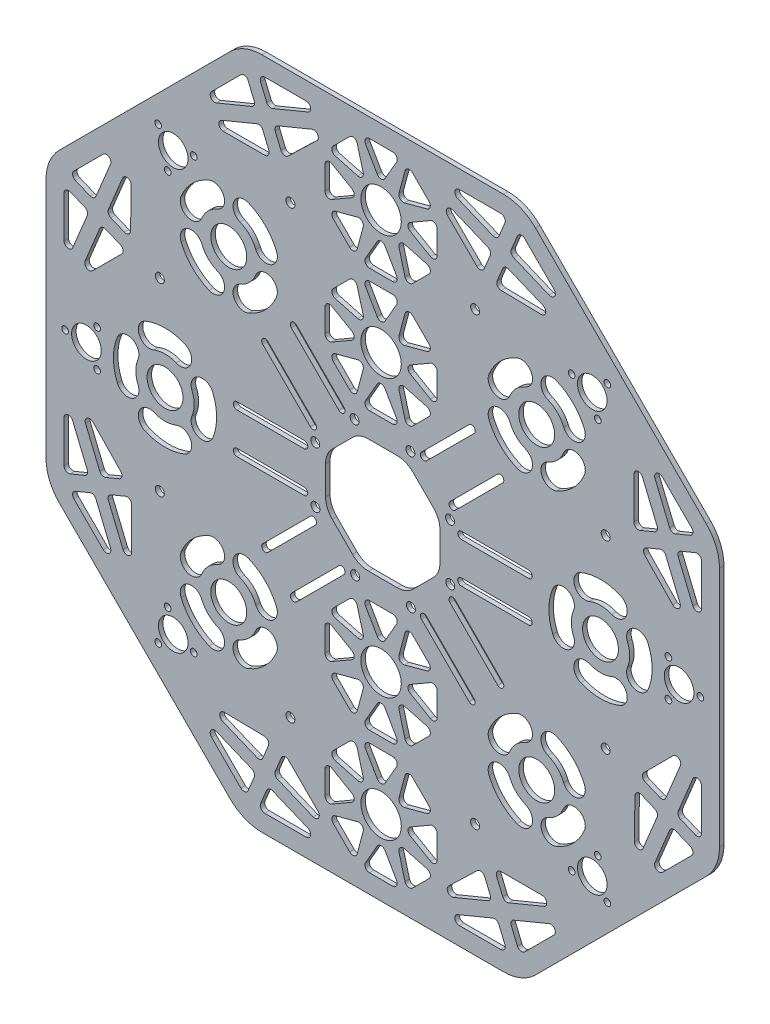
SolidWorks part; units mm, degrees
material "Thornel Mat VMA"
ref_plane "前视基准面" through (0, 0, 0) normal (0, 0, 1) x (1, 0, 0)
ref_plane "上视基准面" through (0, 0, 0) normal (0, 1, 0) x (1, 0, 0)
ref_plane "右视基准面" through (0, 0, 0) normal (1, 0, 0) x (0, 0, -1)
sketch "草图1" plane through (0, 0, 0) normal (0, 0, 1) x (1, 0, 0)
  line L1 (150, 62.132) -> (62.132, 150)
  line L2 (62.132, 150) -> (-62.132, 150)
  line L3 (-62.132, 150) -> (-150, 62.132)
  line L4 (-150, 62.132) -> (-150, -62.132)
  line L5 (-150, -62.132) -> (-62.132, -150)
  line L6 (-62.132, -150) -> (62.132, -150)
  line L7 (62.132, -150) -> (150, -62.132)
  line L8 (150, -62.132) -> (150, 62.132)
  circle A0 centre (0, 0) radius 150 construction
  dimension "D1" = 300
extrude "凸台-拉伸1" add sketch "草图1" along normal blind 2
sketch "草图2" plane through (0, 0, 0) normal (0, 0, -1) x (-1, 0, 0)
  line L0 (-150, -62.132) -> (-150, 62.132) construction
  circle A0 centre (-132, 0) radius 9.5 construction
  circle A1 centre (-132, 0) radius 6.6
  circle A2 centre (-141.5, 0) radius 1.5
  circle A3 centre (-127.25, 8.2272) radius 1.5
  circle A4 centre (-127.25, -8.2272) radius 1.5
  circle A5 centre (-93.3381, 93.3381) radius 6.6
  circle A6 centre (-100.0556, 100.0556) radius 1.5
  circle A7 centre (-84.1618, 95.7969) radius 1.5
  circle A8 centre (-95.7969, 84.1618) radius 1.5
  circle A9 centre (-93.3381, 93.3381) radius 9.5 construction
  circle A15 centre (93.3381, 93.3381) radius 6.6
  circle A16 centre (100.0556, 100.0556) radius 1.5
  circle A17 centre (95.7969, 84.1618) radius 1.5
  circle A18 centre (84.1618, 95.7969) radius 1.5
  circle A19 centre (93.3381, 93.3381) radius 9.5 construction
  circle A20 centre (132, 0) radius 6.6
  circle A21 centre (141.5, 0) radius 1.5
  circle A22 centre (127.25, -8.2272) radius 1.5
  circle A23 centre (127.25, 8.2272) radius 1.5
  circle A24 centre (132, 0) radius 9.5 construction
  circle A25 centre (93.3381, -93.3381) radius 6.6
  circle A26 centre (100.0556, -100.0556) radius 1.5
  circle A27 centre (84.1618, -95.7969) radius 1.5
  circle A28 centre (95.7969, -84.1618) radius 1.5
  circle A29 centre (93.3381, -93.3381) radius 9.5 construction
  circle A35 centre (-93.3381, -93.3381) radius 6.6
  circle A36 centre (-100.0556, -100.0556) radius 1.5
  circle A37 centre (-95.7969, -84.1618) radius 1.5
  circle A38 centre (-84.1618, -95.7969) radius 1.5
  circle A39 centre (-93.3381, -93.3381) radius 9.5 construction
  circle A128 centre (0, 132) radius 6.6
  circle A129 centre (0, 141.5) radius 1.5
  circle A130 centre (8.2272, 127.25) radius 1.5
  circle A131 centre (-8.2272, 127.25) radius 1.5
  circle A132 centre (0, -132) radius 6.6
  circle A133 centre (0, -141.5) radius 1.5
  circle A134 centre (-8.2272, -127.25) radius 1.5
  circle A135 centre (8.2272, -127.25) radius 1.5
  circle A136 centre (0, 132) radius 9.5 construction
  circle A137 centre (0, -132) radius 9.5 construction
  point P6 (0, -132)
  point P7 (-2.8868, -137)
  point P13 (-132, 0)
  point P14 (-137, 2.8868)
  point P19 (-93.3381, 93.3381)
  point P20 (-94.8324, 98.9149)
  point P23 (-93.3381, 93.3381)
  point P24 (0, -132)
  point P25 (0, 132)
  point P26 (2.8868, 137)
  point P31 (-132, 0)
  point P32 (0, 132)
  point P48 (93.3381, 93.3381)
  point P49 (98.9149, 94.8324)
  point P52 (93.3381, 93.3381)
  point P60 (132, 0)
  point P61 (137, -2.8868)
  point P64 (132, 0)
  point P72 (93.3381, -93.3381)
  point P73 (94.8324, -98.9149)
  point P76 (93.3381, -93.3381)
  point P96 (-93.3381, -93.3381)
  point P97 (-98.9149, -94.8324)
  point P100 (-93.3381, -93.3381)
  dimension "D1" = 19
  dimension "D2" = 13.2
  dimension "D3" = 3
  dimension "D5" = 18
  dimension "D4" = 3
  dimension "D6" = 8
extrude "切除-拉伸1" cut sketch "草图2" against normal blind 10
sketch "草图3" plane through (0, 0, 0) normal (0, 0, -1) x (-1, 0, 0)
  line L0 (0, 0) -> (-108.5837, 0) construction
  line L1 (-65, -7.4) -> (-65, -10.6) construction
  line L2 (-65, -7.4) -> (-35, -7.4)
  line L3 (-35, 7.4) -> (-35, 10.6) construction
  line L4 (-65, -10.6) -> (-35, -10.6)
  line L5 (-35, -7.4) -> (-35, -10.6) construction
  line L6 (-65, 7.4) -> (-65, 10.6) construction
  line L7 (-65, 10.6) -> (-35, 10.6)
  line L8 (-65, 7.4) -> (-35, 7.4)
  arc A0 (-65, -7.4) -> (-65, -10.6) centre (-65, -9) ccw
  arc A1 (-35, 10.6) -> (-35, 7.4) centre (-35, 9) cw
  arc A3 (-35, -10.6) -> (-35, -7.4) centre (-35, -9) ccw
  arc A4 (-65, 7.4) -> (-65, 10.6) centre (-65, 9) cw
  dimension "D1" = 9
  dimension "D2" = 3.2
  dimension "D3" = 35
  dimension "D4" = 30
extrude "切除-拉伸2" cut sketch "草图3" against normal blind 10
ref_plane "对角线1" through (0, 0, 0) normal (-0.3827, 0.9239, 0) x (0.9239, 0.3827, 0)
ref_plane "对角线2" through (0, 0, 0) normal (0.3827, 0.9239, 0) x (0.9239, -0.3827, 0)
mirror "镜向2" about plane through (0, 0, 0) normal (-0.3827, 0.9239, 0) of "切除-拉伸2"
mirror "镜向3" about plane through (0, 0, 0) normal (0.3827, 0.9239, 0) of "切除-拉伸2"
mirror "镜向4" about plane through (0, 0, 0) normal (1, 0, 0) of "切除-拉伸2", "镜向3", "镜向2"
fillet "圆角1" radius 20 8 edges at (150, -62.132, 1) (62.132, -150, 1) (-62.132, -150, 1) (-150, -62.132, 1) (-150, 62.132, 1) (-62.132, 150, 1) (150, 62.132, 1) (62.132, 150, 1)
sketch "草图4" plane through (0, 0, 0) normal (0, 0, -1) x (-1, 0, 0)
  line L0 (0, 0) -> (-148.4776, -61.5014) construction
  circle A0 centre (0, 0) radius 107.5 construction
  circle A1 centre (-99.317, -41.1385) radius 2
  arc A2 (-150, -53.8478) -> (-144.1421, -67.9899) centre (-130, -53.8478) ccw construction
  circle A3 centre (-99.317, 41.1385) radius 2
  circle A4 centre (-41.1385, 99.317) radius 2
  circle A5 centre (41.1385, 99.317) radius 2
  circle A6 centre (99.317, 41.1385) radius 2
  circle A7 centre (99.317, -41.1385) radius 2
  circle A8 centre (41.1385, -99.317) radius 2
  circle A9 centre (-41.1385, -99.317) radius 2
  point P25 (0, 0)
  dimension "D1" = 215
  dimension "D2" = 4
  dimension "D3" = 8
extrude "切除-拉伸3" cut sketch "草图4" against normal blind 10
ref_plane "基准面3" through (0, 0, 0) normal (0.7071, 0.7071, 0) x (0.7071, -0.7071, 0)
ref_plane "基准面4" through (0, 0, 0) normal (0.7071, -0.7071, 0) x (0, 0, -1)
sketch "草图5" plane through (0, 0, 2) normal (0, 0, 1) x (1, 0, 0)
  line L1 (25.4769, 10.5529) -> (10.5529, 25.4769)
  line L2 (10.5529, 25.4769) -> (-10.5529, 25.4769)
  line L3 (-10.5529, 25.4769) -> (-25.4769, 10.5529)
  line L4 (-25.4769, 10.5529) -> (-25.4769, -10.5529)
  line L5 (-25.4769, -10.5529) -> (-10.5529, -25.4769)
  line L6 (-10.5529, -25.4769) -> (10.5529, -25.4769)
  line L7 (10.5529, -25.4769) -> (25.4769, -10.5529)
  line L8 (25.4769, -10.5529) -> (25.4769, 10.5529)
  circle A0 centre (0, 0) radius 25.4769 construction
extrude "切除-拉伸4" cut sketch "草图5" against normal blind 35
fillet "圆角2" radius 10 8 edges at (10.5529, -25.4769, 1) (-10.5529, -25.4769, 1) (-25.4769, -10.5529, 1) (-25.4769, 10.5529, 1) (10.5529, 25.4769, 1) (25.4769, 10.5529, 1) (25.4769, -10.5529, 1) (-10.5529, 25.4769, 1)
sketch "草图6" plane through (0, 0, 2) normal (0, 0, 1) x (1, 0, 0)
  line L0 (0, 0) -> (-36.3251, 14.891) construction
  circle A0 centre (0, 0) radius 32.5 construction
  circle A1 centre (-30.0714, 12.3274) radius 2
  circle A2 centre (-12.5469, 29.9804) radius 2
  circle A3 centre (12.3274, 30.0714) radius 2
  circle A4 centre (29.9804, 12.5469) radius 2
  circle A5 centre (30.0714, -12.3274) radius 2
  circle A6 centre (12.5469, -29.9804) radius 2
  circle A7 centre (-12.3274, -30.0714) radius 2
  circle A8 centre (-29.9804, -12.5469) radius 2
  point P22 (0, 0)
  dimension "D1" = 65
  dimension "D2" = 4
  dimension "D3" = 8
extrude "切除-拉伸5" cut sketch "草图6" against normal blind 35
ref_plane "基准面5" through (0, 0, 0) normal (0.7071, -0.7071, 0) x (0, 0, -1)
sketch "草图9" plane through (0, 0, 2) normal (0, 0, 1) x (1, 0, 0)
  line L0 (0, 0) -> (150, 0) construction
  line L1 (97, 0) -> (103.8883, -16.6298) construction
  line L2 (0, 0) -> (106.066, -106.066) construction
  line L3 (90.1117, -16.6298) -> (97, 0) construction
  line L4 (68.5894, -68.5894) -> (61.7011, -85.2192) construction
  line L5 (150, -53.8478) -> (150, 53.8478) construction
  line L6 (97, 0) -> (97, -36) construction
  line L7 (51.9595, -75.4777) -> (68.5894, -68.5894) construction
  line L8 (68.5894, -68.5894) -> (43.1335, -94.0452) construction
  line L13 (0, 0) -> (-106.066, -106.066) construction
  line L14 (-68.5894, -68.5894) -> (-85.2192, -61.7011) construction
  line L15 (-75.4777, -51.9595) -> (-68.5894, -68.5894) construction
  line L16 (-68.5894, -68.5894) -> (-94.0452, -43.1335) construction
  line L17 (0, 0) -> (-150, 0) construction
  line L18 (-97, 0) -> (-103.8883, 16.6298) construction
  line L19 (-90.1117, 16.6298) -> (-97, 0) construction
  line L20 (-97, 0) -> (-97, 36) construction
  line L21 (0, 0) -> (-106.066, 106.066) construction
  line L22 (-68.5894, 68.5894) -> (-61.7011, 85.2192) construction
  line L23 (-51.9595, 75.4777) -> (-68.5894, 68.5894) construction
  line L24 (-68.5894, 68.5894) -> (-43.1335, 94.0452) construction
  line L29 (0, 0) -> (106.066, 106.066) construction
  line L30 (68.5894, 68.5894) -> (85.2192, 61.7011) construction
  line L31 (75.4777, 51.9595) -> (68.5894, 68.5894) construction
  line L32 (68.5894, 68.5894) -> (94.0452, 43.1335) construction
  line L33 (0, 0) -> (0, -150) construction
  line L34 (0, -97) -> (-16.6298, -103.8883) construction
  line L35 (-16.6298, -90.1117) -> (0, -97) construction
  line L36 (0, -97) -> (-36, -97) construction
  line L37 (0, 0) -> (0, 150) construction
  line L38 (0, 97) -> (16.6298, 103.8883) construction
  line L39 (16.6298, 90.1117) -> (0, 97) construction
  line L40 (0, 97) -> (36, 97) construction
  circle A0 centre (97, 0) radius 8
  arc A1 (103.8883, -16.6298) -> (90.1117, -16.6298) centre (97, 0) cw construction
  arc A2 (88.1983, -21.2492) -> (105.8017, -21.2492) centre (97, 0) ccw
  arc A3 (92.0251, -12.0104) -> (101.9749, -12.0104) centre (97, 0) ccw
  arc A4 (92.0251, -12.0104) -> (88.1983, -21.2492) centre (90.1117, -16.6298) ccw
  arc A5 (105.8017, -21.2492) -> (101.9749, -12.0104) centre (103.8883, -16.6298) ccw
  arc A6 (80.3702, -6.8883) -> (80.3702, 6.8883) centre (97, 0) cw construction
  arc A7 (75.7508, 8.8017) -> (75.7508, -8.8017) centre (97, 0) ccw
  arc A8 (84.9896, 4.9749) -> (84.9896, -4.9749) centre (97, 0) ccw
  arc A9 (84.9896, 4.9749) -> (75.7508, 8.8017) centre (80.3702, 6.8883) ccw
  arc A10 (75.7508, -8.8017) -> (84.9896, -4.9749) centre (80.3702, -6.8883) ccw
  arc A11 (90.1117, 16.6298) -> (103.8883, 16.6298) centre (97, 0) cw construction
  arc A12 (105.8017, 21.2492) -> (88.1983, 21.2492) centre (97, 0) ccw
  arc A13 (101.9749, 12.0104) -> (92.0251, 12.0104) centre (97, 0) ccw
  arc A14 (101.9749, 12.0104) -> (105.8017, 21.2492) centre (103.8883, 16.6298) ccw
  arc A15 (88.1983, 21.2492) -> (92.0251, 12.0104) centre (90.1117, 16.6298) ccw
  arc A16 (113.6298, 6.8883) -> (113.6298, -6.8883) centre (97, 0) cw construction
  arc A17 (118.2492, -8.8017) -> (118.2492, 8.8017) centre (97, 0) ccw
  arc A18 (109.0104, -4.9749) -> (109.0104, 4.9749) centre (97, 0) ccw
  arc A19 (109.0104, -4.9749) -> (118.2492, -8.8017) centre (113.6298, -6.8883) ccw
  arc A20 (118.2492, 8.8017) -> (109.0104, 4.9749) centre (113.6298, 6.8883) ccw
  circle A21 centre (68.5894, -68.5894) radius 8
  arc A22 (61.7011, -85.2192) -> (51.9595, -75.4777) centre (68.5894, -68.5894) cw construction
  arc A23 (47.3401, -77.3911) -> (59.7876, -89.8386) centre (68.5894, -68.5894) ccw
  arc A24 (56.5789, -73.5642) -> (63.6145, -80.5998) centre (68.5894, -68.5894) ccw
  arc A25 (56.5789, -73.5642) -> (47.3401, -77.3911) centre (51.9595, -75.4777) ccw
  arc A26 (59.7876, -89.8386) -> (63.6145, -80.5998) centre (61.7011, -85.2192) ccw
  arc A27 (51.9595, -61.7011) -> (61.7011, -51.9595) centre (68.5894, -68.5894) cw construction
  arc A28 (59.7876, -47.3401) -> (47.3401, -59.7876) centre (68.5894, -68.5894) ccw
  arc A29 (63.6145, -56.5789) -> (56.5789, -63.6145) centre (68.5894, -68.5894) ccw
  arc A30 (63.6145, -56.5789) -> (59.7876, -47.3401) centre (61.7011, -51.9595) ccw
  arc A31 (47.3401, -59.7876) -> (56.5789, -63.6145) centre (51.9595, -61.7011) ccw
  arc A32 (75.4777, -51.9595) -> (85.2192, -61.7011) centre (68.5894, -68.5894) cw construction
  arc A33 (89.8386, -59.7876) -> (77.3911, -47.3401) centre (68.5894, -68.5894) ccw
  arc A34 (80.5998, -63.6145) -> (73.5642, -56.5789) centre (68.5894, -68.5894) ccw
  arc A35 (80.5998, -63.6145) -> (89.8386, -59.7876) centre (85.2192, -61.7011) ccw
  arc A36 (77.3911, -47.3401) -> (73.5642, -56.5789) centre (75.4777, -51.9595) ccw
  arc A37 (85.2192, -75.4777) -> (75.4777, -85.2192) centre (68.5894, -68.5894) cw construction
  arc A38 (77.3911, -89.8386) -> (89.8386, -77.3911) centre (68.5894, -68.5894) ccw
  arc A39 (73.5642, -80.5998) -> (80.5998, -73.5642) centre (68.5894, -68.5894) ccw
  arc A40 (73.5642, -80.5998) -> (77.3911, -89.8386) centre (75.4777, -85.2192) ccw
  arc A41 (89.8386, -77.3911) -> (80.5998, -73.5642) centre (85.2192, -75.4777) ccw
  circle A63 centre (-68.5894, -68.5894) radius 8
  arc A64 (-85.2192, -61.7011) -> (-75.4777, -51.9595) centre (-68.5894, -68.5894) cw construction
  arc A65 (-77.3911, -47.3401) -> (-89.8386, -59.7876) centre (-68.5894, -68.5894) ccw
  arc A66 (-73.5642, -56.5789) -> (-80.5998, -63.6145) centre (-68.5894, -68.5894) ccw
  arc A67 (-73.5642, -56.5789) -> (-77.3911, -47.3401) centre (-75.4777, -51.9595) ccw
  arc A68 (-89.8386, -59.7876) -> (-80.5998, -63.6145) centre (-85.2192, -61.7011) ccw
  arc A69 (-61.7011, -51.9595) -> (-51.9595, -61.7011) centre (-68.5894, -68.5894) cw construction
  arc A70 (-47.3401, -59.7876) -> (-59.7876, -47.3401) centre (-68.5894, -68.5894) ccw
  arc A71 (-56.5789, -63.6145) -> (-63.6145, -56.5789) centre (-68.5894, -68.5894) ccw
  arc A72 (-56.5789, -63.6145) -> (-47.3401, -59.7876) centre (-51.9595, -61.7011) ccw
  arc A73 (-59.7876, -47.3401) -> (-63.6145, -56.5789) centre (-61.7011, -51.9595) ccw
  arc A74 (-51.9595, -75.4777) -> (-61.7011, -85.2192) centre (-68.5894, -68.5894) cw construction
  arc A75 (-59.7876, -89.8386) -> (-47.3401, -77.3911) centre (-68.5894, -68.5894) ccw
  arc A76 (-63.6145, -80.5998) -> (-56.5789, -73.5642) centre (-68.5894, -68.5894) ccw
  arc A77 (-63.6145, -80.5998) -> (-59.7876, -89.8386) centre (-61.7011, -85.2192) ccw
  arc A78 (-47.3401, -77.3911) -> (-56.5789, -73.5642) centre (-51.9595, -75.4777) ccw
  arc A79 (-75.4777, -85.2192) -> (-85.2192, -75.4777) centre (-68.5894, -68.5894) cw construction
  arc A80 (-89.8386, -77.3911) -> (-77.3911, -89.8386) centre (-68.5894, -68.5894) ccw
  arc A81 (-80.5998, -73.5642) -> (-73.5642, -80.5998) centre (-68.5894, -68.5894) ccw
  arc A82 (-80.5998, -73.5642) -> (-89.8386, -77.3911) centre (-85.2192, -75.4777) ccw
  arc A83 (-77.3911, -89.8386) -> (-73.5642, -80.5998) centre (-75.4777, -85.2192) ccw
  circle A84 centre (-97, 0) radius 8
  arc A85 (-103.8883, 16.6298) -> (-90.1117, 16.6298) centre (-97, 0) cw construction
  arc A86 (-88.1983, 21.2492) -> (-105.8017, 21.2492) centre (-97, 0) ccw
  arc A87 (-92.0251, 12.0104) -> (-101.9749, 12.0104) centre (-97, 0) ccw
  arc A88 (-92.0251, 12.0104) -> (-88.1983, 21.2492) centre (-90.1117, 16.6298) ccw
  arc A89 (-105.8017, 21.2492) -> (-101.9749, 12.0104) centre (-103.8883, 16.6298) ccw
  arc A90 (-80.3702, 6.8883) -> (-80.3702, -6.8883) centre (-97, 0) cw construction
  arc A91 (-75.7508, -8.8017) -> (-75.7508, 8.8017) centre (-97, 0) ccw
  arc A92 (-84.9896, -4.9749) -> (-84.9896, 4.9749) centre (-97, 0) ccw
  arc A93 (-84.9896, -4.9749) -> (-75.7508, -8.8017) centre (-80.3702, -6.8883) ccw
  arc A94 (-75.7508, 8.8017) -> (-84.9896, 4.9749) centre (-80.3702, 6.8883) ccw
  arc A95 (-90.1117, -16.6298) -> (-103.8883, -16.6298) centre (-97, 0) cw construction
  arc A96 (-105.8017, -21.2492) -> (-88.1983, -21.2492) centre (-97, 0) ccw
  arc A97 (-101.9749, -12.0104) -> (-92.0251, -12.0104) centre (-97, 0) ccw
  arc A98 (-101.9749, -12.0104) -> (-105.8017, -21.2492) centre (-103.8883, -16.6298) ccw
  arc A99 (-88.1983, -21.2492) -> (-92.0251, -12.0104) centre (-90.1117, -16.6298) ccw
  arc A100 (-113.6298, -6.8883) -> (-113.6298, 6.8883) centre (-97, 0) cw construction
  arc A101 (-118.2492, 8.8017) -> (-118.2492, -8.8017) centre (-97, 0) ccw
  arc A102 (-109.0104, 4.9749) -> (-109.0104, -4.9749) centre (-97, 0) ccw
  arc A103 (-109.0104, 4.9749) -> (-118.2492, 8.8017) centre (-113.6298, 6.8883) ccw
  arc A104 (-118.2492, -8.8017) -> (-109.0104, -4.9749) centre (-113.6298, -6.8883) ccw
  circle A105 centre (-68.5894, 68.5894) radius 8
  arc A106 (-61.7011, 85.2192) -> (-51.9595, 75.4777) centre (-68.5894, 68.5894) cw construction
  arc A107 (-47.3401, 77.3911) -> (-59.7876, 89.8386) centre (-68.5894, 68.5894) ccw
  arc A108 (-56.5789, 73.5642) -> (-63.6145, 80.5998) centre (-68.5894, 68.5894) ccw
  arc A109 (-56.5789, 73.5642) -> (-47.3401, 77.3911) centre (-51.9595, 75.4777) ccw
  arc A110 (-59.7876, 89.8386) -> (-63.6145, 80.5998) centre (-61.7011, 85.2192) ccw
  arc A111 (-51.9595, 61.7011) -> (-61.7011, 51.9595) centre (-68.5894, 68.5894) cw construction
  arc A112 (-59.7876, 47.3401) -> (-47.3401, 59.7876) centre (-68.5894, 68.5894) ccw
  arc A113 (-63.6145, 56.5789) -> (-56.5789, 63.6145) centre (-68.5894, 68.5894) ccw
  arc A114 (-63.6145, 56.5789) -> (-59.7876, 47.3401) centre (-61.7011, 51.9595) ccw
  arc A115 (-47.3401, 59.7876) -> (-56.5789, 63.6145) centre (-51.9595, 61.7011) ccw
  arc A116 (-75.4777, 51.9595) -> (-85.2192, 61.7011) centre (-68.5894, 68.5894) cw construction
  arc A117 (-89.8386, 59.7876) -> (-77.3911, 47.3401) centre (-68.5894, 68.5894) ccw
  arc A118 (-80.5998, 63.6145) -> (-73.5642, 56.5789) centre (-68.5894, 68.5894) ccw
  arc A119 (-80.5998, 63.6145) -> (-89.8386, 59.7876) centre (-85.2192, 61.7011) ccw
  arc A120 (-77.3911, 47.3401) -> (-73.5642, 56.5789) centre (-75.4777, 51.9595) ccw
  arc A121 (-85.2192, 75.4777) -> (-75.4777, 85.2192) centre (-68.5894, 68.5894) cw construction
  arc A122 (-77.3911, 89.8386) -> (-89.8386, 77.3911) centre (-68.5894, 68.5894) ccw
  arc A123 (-73.5642, 80.5998) -> (-80.5998, 73.5642) centre (-68.5894, 68.5894) ccw
  arc A124 (-73.5642, 80.5998) -> (-77.3911, 89.8386) centre (-75.4777, 85.2192) ccw
  arc A125 (-89.8386, 77.3911) -> (-80.5998, 73.5642) centre (-85.2192, 75.4777) ccw
  circle A147 centre (68.5894, 68.5894) radius 8
  arc A148 (85.2192, 61.7011) -> (75.4777, 51.9595) centre (68.5894, 68.5894) cw construction
  arc A149 (77.3911, 47.3401) -> (89.8386, 59.7876) centre (68.5894, 68.5894) ccw
  arc A150 (73.5642, 56.5789) -> (80.5998, 63.6145) centre (68.5894, 68.5894) ccw
  arc A151 (73.5642, 56.5789) -> (77.3911, 47.3401) centre (75.4777, 51.9595) ccw
  arc A152 (89.8386, 59.7876) -> (80.5998, 63.6145) centre (85.2192, 61.7011) ccw
  arc A153 (61.7011, 51.9595) -> (51.9595, 61.7011) centre (68.5894, 68.5894) cw construction
  arc A154 (47.3401, 59.7876) -> (59.7876, 47.3401) centre (68.5894, 68.5894) ccw
  arc A155 (56.5789, 63.6145) -> (63.6145, 56.5789) centre (68.5894, 68.5894) ccw
  arc A156 (56.5789, 63.6145) -> (47.3401, 59.7876) centre (51.9595, 61.7011) ccw
  arc A157 (59.7876, 47.3401) -> (63.6145, 56.5789) centre (61.7011, 51.9595) ccw
  arc A158 (51.9595, 75.4777) -> (61.7011, 85.2192) centre (68.5894, 68.5894) cw construction
  arc A159 (59.7876, 89.8386) -> (47.3401, 77.3911) centre (68.5894, 68.5894) ccw
  arc A160 (63.6145, 80.5998) -> (56.5789, 73.5642) centre (68.5894, 68.5894) ccw
  arc A161 (63.6145, 80.5998) -> (59.7876, 89.8386) centre (61.7011, 85.2192) ccw
  arc A162 (47.3401, 77.3911) -> (56.5789, 73.5642) centre (51.9595, 75.4777) ccw
  arc A163 (75.4777, 85.2192) -> (85.2192, 75.4777) centre (68.5894, 68.5894) cw construction
  arc A164 (89.8386, 77.3911) -> (77.3911, 89.8386) centre (68.5894, 68.5894) ccw
  arc A165 (80.5998, 73.5642) -> (73.5642, 80.5998) centre (68.5894, 68.5894) ccw
  arc A166 (80.5998, 73.5642) -> (89.8386, 77.3911) centre (85.2192, 75.4777) ccw
  arc A167 (77.3911, 89.8386) -> (73.5642, 80.5998) centre (75.4777, 85.2192) ccw
  circle A168 centre (0, -97) radius 8
  circle A173 centre (0, 97) radius 8
  arc A174 (-16.6298, -103.8883) -> (-16.6298, -90.1117) centre (0, -97) cw construction
  arc A175 (-21.2492, -88.1983) -> (-21.2492, -105.8017) centre (0, -97) ccw
  arc A176 (-12.0104, -92.0251) -> (-12.0104, -101.9749) centre (0, -97) ccw
  arc A177 (-12.0104, -92.0251) -> (-21.2492, -88.1983) centre (-16.6298, -90.1117) ccw
  arc A178 (-21.2492, -105.8017) -> (-12.0104, -101.9749) centre (-16.6298, -103.8883) ccw
  arc A179 (-6.8883, -80.3702) -> (6.8883, -80.3702) centre (0, -97) cw construction
  arc A180 (8.8017, -75.7508) -> (-8.8017, -75.7508) centre (0, -97) ccw
  arc A181 (4.9749, -84.9896) -> (-4.9749, -84.9896) centre (0, -97) ccw
  arc A182 (4.9749, -84.9896) -> (8.8017, -75.7508) centre (6.8883, -80.3702) ccw
  arc A183 (-8.8017, -75.7508) -> (-4.9749, -84.9896) centre (-6.8883, -80.3702) ccw
  arc A184 (16.6298, -90.1117) -> (16.6298, -103.8883) centre (0, -97) cw construction
  arc A185 (21.2492, -105.8017) -> (21.2492, -88.1983) centre (0, -97) ccw
  arc A186 (12.0104, -101.9749) -> (12.0104, -92.0251) centre (0, -97) ccw
  arc A187 (12.0104, -101.9749) -> (21.2492, -105.8017) centre (16.6298, -103.8883) ccw
  arc A188 (21.2492, -88.1983) -> (12.0104, -92.0251) centre (16.6298, -90.1117) ccw
  arc A189 (6.8883, -113.6298) -> (-6.8883, -113.6298) centre (0, -97) cw construction
  arc A190 (-8.8017, -118.2492) -> (8.8017, -118.2492) centre (0, -97) ccw
  arc A191 (-4.9749, -109.0104) -> (4.9749, -109.0104) centre (0, -97) ccw
  arc A192 (-4.9749, -109.0104) -> (-8.8017, -118.2492) centre (-6.8883, -113.6298) ccw
  arc A193 (8.8017, -118.2492) -> (4.9749, -109.0104) centre (6.8883, -113.6298) ccw
  arc A194 (16.6298, 103.8883) -> (16.6298, 90.1117) centre (0, 97) cw construction
  arc A195 (21.2492, 88.1983) -> (21.2492, 105.8017) centre (0, 97) ccw
  arc A196 (12.0104, 92.0251) -> (12.0104, 101.9749) centre (0, 97) ccw
  arc A197 (12.0104, 92.0251) -> (21.2492, 88.1983) centre (16.6298, 90.1117) ccw
  arc A198 (21.2492, 105.8017) -> (12.0104, 101.9749) centre (16.6298, 103.8883) ccw
  arc A199 (6.8883, 80.3702) -> (-6.8883, 80.3702) centre (0, 97) cw construction
  arc A200 (-8.8017, 75.7508) -> (8.8017, 75.7508) centre (0, 97) ccw
  arc A201 (-4.9749, 84.9896) -> (4.9749, 84.9896) centre (0, 97) ccw
  arc A202 (-4.9749, 84.9896) -> (-8.8017, 75.7508) centre (-6.8883, 80.3702) ccw
  arc A203 (8.8017, 75.7508) -> (4.9749, 84.9896) centre (6.8883, 80.3702) ccw
  arc A204 (-16.6298, 90.1117) -> (-16.6298, 103.8883) centre (0, 97) cw construction
  arc A205 (-21.2492, 105.8017) -> (-21.2492, 88.1983) centre (0, 97) ccw
  arc A206 (-12.0104, 101.9749) -> (-12.0104, 92.0251) centre (0, 97) ccw
  arc A207 (-12.0104, 101.9749) -> (-21.2492, 105.8017) centre (-16.6298, 103.8883) ccw
  arc A208 (-21.2492, 88.1983) -> (-12.0104, 92.0251) centre (-16.6298, 90.1117) ccw
  arc A209 (-6.8883, 113.6298) -> (6.8883, 113.6298) centre (0, 97) cw construction
  arc A210 (8.8017, 118.2492) -> (-8.8017, 118.2492) centre (0, 97) ccw
  arc A211 (4.9749, 109.0104) -> (-4.9749, 109.0104) centre (0, 97) ccw
  arc A212 (4.9749, 109.0104) -> (8.8017, 118.2492) centre (6.8883, 113.6298) ccw
  arc A213 (-8.8017, 118.2492) -> (-4.9749, 109.0104) centre (-6.8883, 113.6298) ccw
  point P8 (97, -18)
  point P21 (79, 0)
  point P29 (97, 18)
  point P36 (115, 0)
  point P41 (97, 0)
  point P46 (55.8614, -81.3173)
  point P53 (25, -99)
  point P57 (55.8614, -55.8614)
  point P65 (81.3173, -55.8614)
  point P72 (81.3173, -81.3173)
  point P77 (68.5894, -68.5894)
  point P78 (0, -97)
  point P82 (-25, -99)
  point P85 (0, -74)
  point P86 (0, -79)
  point P91 (25, 99)
  point P93 (18, 97)
  point P95 (25, -99)
  point P98 (18, -97)
  point P103 (0, -124)
  point P107 (0, -115)
  point P113 (0, 74)
  point P118 (0, 79)
  point P125 (-81.3173, -55.8614)
  point P135 (-55.8614, -55.8614)
  point P137 (-25, 99)
  point P141 (-25, -99)
  point P145 (-55.8614, -81.3173)
  point P152 (-81.3173, -81.3173)
  point P157 (-68.5894, -68.5894)
  point P163 (-97, 18)
  point P173 (0, 0)
  point P174 (25, 99)
  point P175 (-79, 0)
  point P183 (-97, -18)
  point P190 (-115, 0)
  point P195 (-97, 0)
  point P201 (-55.8614, 81.3173)
  point P211 (-55.8614, 55.8614)
  point P219 (-81.3173, 55.8614)
  point P226 (-81.3173, 81.3173)
  point P231 (-68.5894, 68.5894)
  point P232 (0, 97)
  point P235 (-25, 99)
  point P241 (-18, 97)
  point P247 (0, 124)
  point P254 (0, 115)
  point P275 (81.3173, 55.8614)
  point P285 (55.8614, 55.8614)
  point P293 (55.8614, 81.3173)
  point P299 (0, 0)
  point P301 (81.3173, 81.3173)
  point P306 (68.5894, 68.5894)
  point P307 (0, 0)
  point P308 (-18, -97)
  point P347 (-25, -99)
  point P355 (25, -99)
  point P363 (25, 99)
  point P371 (-25, 99)
  point P379 (-25, -99)
  point P387 (25, -99)
  point P395 (25, 99)
  point P403 (-25, 99)
  point P411 (-25, -99)
  point P419 (25, -99)
  point P427 (25, 99)
  point P435 (-25, 99)
  point P443 (-25, -99)
  point P451 (25, -99)
  point P459 (25, 99)
  point P467 (-25, 99)
  point P475 (-25, -99)
  point P483 (25, -99)
  point P491 (25, 99)
  point P499 (-25, 99)
  point P507 (-25, -99)
  point P515 (25, -99)
  point P523 (25, 99)
  point P531 (-25, 99)
  point P539 (-25, -99)
  point P547 (25, -99)
  point P555 (25, 99)
  point P563 (-25, 99)
  point P587 (-18, -97)
  point P595 (0, -79)
  point P603 (18, -97)
  point P611 (0, -115)
  point P619 (18, 97)
  point P627 (0, 79)
  point P635 (-18, 97)
  point P643 (0, 115)
  dimension "D2" = 16
  dimension "D4" = 5
  dimension "D3" = 18
  dimension "D5" = 45
  dimension "D7" = 8
  dimension "D1" = 97
  dimension "D6" = 4
extrude "切除-拉伸8" cut sketch "草图9" against normal blind 10
sketch "草图10" plane through (0, 0, 2) normal (0, 0, 1) x (1, 0, 0)
  line L0 (6.3271, -54.5539) -> (23.0574, -50.071)
  line L1 (-0.744, -51.6249) -> (7.9163, -36.6249)
  line L2 (7.9163, -36.6249) -> (-9.4042, -36.6249)
  line L3 (-9.4042, -36.6249) -> (-0.744, -51.6249)
  line L4 (10.81, -37.8236) -> (6.3271, -54.5539)
  line L5 (23.0574, -50.071) -> (10.81, -37.8236)
  line L6 (9.256, -61.6249) -> (24.256, -70.2852)
  line L7 (24.256, -52.9647) -> (9.256, -61.6249)
  line L8 (24.256, -70.2852) -> (24.256, -52.9647)
  line L9 (6.3271, -68.696) -> (10.81, -85.4263)
  line L10 (23.0574, -73.1789) -> (6.3271, -68.696)
  line L11 (10.81, -85.4263) -> (23.0574, -73.1789)
  line L12 (-0.744, -71.6249) -> (-9.4042, -86.6249)
  line L13 (7.9163, -86.6249) -> (-0.744, -71.6249)
  line L14 (-9.4042, -86.6249) -> (7.9163, -86.6249)
  line L15 (-7.8151, -68.696) -> (-24.5454, -73.1789)
  line L16 (-12.2979, -85.4263) -> (-7.8151, -68.696)
  line L17 (-24.5454, -73.1789) -> (-12.2979, -85.4263)
  line L18 (-10.744, -61.6249) -> (-25.744, -52.9647)
  line L19 (-25.744, -70.2852) -> (-10.744, -61.6249)
  line L20 (-25.744, -52.9647) -> (-25.744, -70.2852)
  line L21 (-7.8151, -54.5539) -> (-12.2979, -37.8236)
  line L22 (-24.5454, -50.071) -> (-7.8151, -54.5539)
  line L23 (-12.2979, -37.8236) -> (-24.5454, -50.071)
  line L24 (6.3271, -109.5539) -> (23.0574, -105.071)
  line L25 (-0.744, -106.6249) -> (7.9163, -91.6249)
  line L26 (7.9163, -91.6249) -> (-9.4042, -91.6249)
  line L27 (-9.4042, -91.6249) -> (-0.744, -106.6249)
  line L28 (10.81, -92.8236) -> (6.3271, -109.5539)
  line L29 (23.0574, -105.071) -> (10.81, -92.8236)
  line L30 (9.256, -116.6249) -> (24.256, -125.2852)
  line L31 (24.256, -107.9647) -> (9.256, -116.6249)
  line L32 (24.256, -125.2852) -> (24.256, -107.9647)
  line L33 (6.3271, -123.696) -> (10.81, -140.4263)
  line L34 (23.0574, -128.1789) -> (6.3271, -123.696)
  line L35 (10.81, -140.4263) -> (23.0574, -128.1789)
  line L36 (-0.744, -126.6249) -> (-9.4042, -141.6249)
  line L37 (7.9163, -141.6249) -> (-0.744, -126.6249)
  line L38 (-9.4042, -141.6249) -> (7.9163, -141.6249)
  line L39 (-7.8151, -123.696) -> (-24.5454, -128.1789)
  line L40 (-12.2979, -140.4263) -> (-7.8151, -123.696)
  line L41 (-24.5454, -128.1789) -> (-12.2979, -140.4263)
  line L42 (-10.744, -116.6249) -> (-25.744, -107.9647)
  line L43 (-25.744, -125.2852) -> (-10.744, -116.6249)
  line L44 (-25.744, -107.9647) -> (-25.744, -125.2852)
  line L45 (-7.8151, -109.5539) -> (-12.2979, -92.8236)
  line L46 (-24.5454, -105.071) -> (-7.8151, -109.5539)
  line L47 (-12.2979, -92.8236) -> (-24.5454, -105.071)
  line L48 (83.4071, -117.4112) -> (61.1144, -139.7039)
  line L49 (55.5711, -142) -> (24.0446, -142)
  line L50 (21.7485, -136.4567) -> (44.2653, -114.7053)
  line L51 (49.5844, -111.868) -> (81.111, -111.868)
  line L52 (67.9899, -144.1421) -> (144.1421, -67.9899) construction
  line L53 (-53.8478, -150) -> (53.8478, -150) construction
  line L54 (58.4356, -141.0761) -> (46.7199, -112.7918) construction
  line L55 (86.7199, -112.7918) -> (18.4356, -141.0761) construction
  line L56 (81.111, -111.868) -> (54.2014, -123.0143)
  line L57 (83.4071, -117.4112) -> (56.4975, -128.5576)
  line L58 (61.1144, -139.7039) -> (56.4975, -128.5576)
  line L59 (55.5711, -142) -> (50.9542, -130.8537)
  line L60 (54.2014, -123.0143) -> (49.5844, -111.868)
  line L61 (87.868, -115.5635) -> (19.5837, -143.8478) construction
  line L62 (85.5719, -110.0202) -> (17.2876, -138.3045) construction
  line L63 (61.2073, -139.9281) -> (49.4916, -111.6438) construction
  line L64 (55.664, -142.2242) -> (43.9483, -113.9399) construction
  line L65 (48.6581, -125.3104) -> (21.7485, -136.4567)
  line L66 (48.6581, -125.3104) -> (44.2653, -114.7053)
  line L67 (50.9542, -130.8537) -> (24.0446, -142)
  line L68 (-24.0446, -142) -> (-55.5711, -142)
  line L69 (-61.1144, -139.7039) -> (-83.4071, -117.4112)
  line L70 (-81.111, -111.868) -> (-49.8086, -112.4092)
  line L71 (-44.0411, -114.1641) -> (-21.7485, -136.4567)
  line L72 (-21.7485, -136.4567) -> (-48.6581, -125.3104)
  line L73 (-24.0446, -142) -> (-50.9542, -130.8537)
  line L74 (-55.5711, -142) -> (-50.9542, -130.8537)
  line L75 (-61.1144, -139.7039) -> (-56.4975, -128.5576)
  line L76 (-48.6581, -125.3104) -> (-44.0411, -114.1641)
  line L77 (-54.2014, -123.0143) -> (-81.111, -111.868)
  line L78 (-54.2014, -123.0143) -> (-49.8086, -112.4092)
  line L79 (-56.4975, -128.5576) -> (-83.4071, -117.4112)
  line L80 (-58.4356, -141.0761) -> (-46.7199, -112.7918) construction
  line L81 (-18.4356, -141.0761) -> (-86.7199, -112.7918) construction
  line L82 (-117.4112, -83.4071) -> (-139.7039, -61.1144)
  line L83 (-142, -55.5711) -> (-142, -24.0446)
  line L84 (-136.4567, -21.7485) -> (-114.7053, -44.2653)
  line L85 (-111.868, -49.5844) -> (-111.868, -81.111)
  line L86 (-111.868, -81.111) -> (-123.0143, -54.2014)
  line L87 (-117.4112, -83.4071) -> (-128.5576, -56.4975)
  line L88 (-139.7039, -61.1144) -> (-128.5576, -56.4975)
  line L89 (-142, -55.5711) -> (-130.8537, -50.9542)
  line L90 (-123.0143, -54.2014) -> (-111.868, -49.5844)
  line L91 (-125.3104, -48.6581) -> (-136.4567, -21.7485)
  line L92 (-125.3104, -48.6581) -> (-114.7053, -44.2653)
  line L93 (-130.8537, -50.9542) -> (-142, -24.0446)
  line L94 (-141.0761, -58.4356) -> (-112.7918, -46.7199) construction
  line L95 (-112.7918, -86.7199) -> (-141.0761, -18.4356) construction
  line L96 (-142, 24.0446) -> (-142, 55.5711)
  line L97 (-139.7039, 61.1144) -> (-117.4112, 83.4071)
  line L98 (-111.868, 81.111) -> (-112.4092, 49.8086)
  line L99 (0, 0) -> (19.256, 0) construction
  line L100 (-114.1641, 44.0411) -> (-136.4567, 21.7485)
  line L101 (-136.4567, 21.7485) -> (-125.3104, 48.6581)
  line L102 (-142, 24.0446) -> (-130.8537, 50.9542)
  line L103 (-142, 55.5711) -> (-130.8537, 50.9542)
  line L104 (-139.7039, 61.1144) -> (-128.5576, 56.4975)
  line L105 (-125.3104, 48.6581) -> (-114.1641, 44.0411)
  line L106 (-123.0143, 54.2014) -> (-111.868, 81.111)
  line L107 (-123.0143, 54.2014) -> (-112.4092, 49.8086)
  line L108 (-128.5576, 56.4975) -> (-117.4112, 83.4071)
  line L109 (-141.0761, 58.4356) -> (-112.7918, 46.7199) construction
  line L110 (-141.0761, 18.4356) -> (-112.7918, 86.7199) construction
  line L111 (-83.4071, 117.4112) -> (-61.1144, 139.7039)
  line L112 (-55.5711, 142) -> (-24.0446, 142)
  line L113 (-21.7485, 136.4567) -> (-44.2653, 114.7053)
  line L114 (-49.5844, 111.868) -> (-81.111, 111.868)
  line L115 (-81.111, 111.868) -> (-54.2014, 123.0143)
  line L116 (-83.4071, 117.4112) -> (-56.4975, 128.5576)
  line L117 (-61.1144, 139.7039) -> (-56.4975, 128.5576)
  line L118 (-55.5711, 142) -> (-50.9542, 130.8537)
  line L119 (-54.2014, 123.0143) -> (-49.5844, 111.868)
  line L120 (-48.6581, 125.3104) -> (-21.7485, 136.4567)
  line L121 (-48.6581, 125.3104) -> (-44.2653, 114.7053)
  line L122 (-50.9542, 130.8537) -> (-24.0446, 142)
  line L123 (-58.4356, 141.0761) -> (-46.7199, 112.7918) construction
  line L124 (-86.7199, 112.7918) -> (-18.4356, 141.0761) construction
  line L125 (24.0446, 142) -> (55.5711, 142)
  line L126 (61.1144, 139.7039) -> (83.4071, 117.4112)
  line L127 (81.111, 111.868) -> (49.8086, 112.4092)
  line L128 (44.0411, 114.1641) -> (21.7485, 136.4567)
  line L129 (21.7485, 136.4567) -> (48.6581, 125.3104)
  line L130 (24.0446, 142) -> (50.9542, 130.8537)
  line L131 (55.5711, 142) -> (50.9542, 130.8537)
  line L132 (61.1144, 139.7039) -> (56.4975, 128.5576)
  line L133 (48.6581, 125.3104) -> (44.0411, 114.1641)
  line L134 (54.2014, 123.0143) -> (81.111, 111.868)
  line L135 (54.2014, 123.0143) -> (49.8086, 112.4092)
  line L136 (56.4975, 128.5576) -> (83.4071, 117.4112)
  line L137 (58.4356, 141.0761) -> (46.7199, 112.7918) construction
  line L138 (18.4356, 141.0761) -> (86.7199, 112.7918) construction
  line L139 (117.4112, 83.4071) -> (139.7039, 61.1144)
  line L140 (142, 55.5711) -> (142, 24.0446)
  line L141 (136.4567, 21.7485) -> (114.7053, 44.2653)
  line L142 (111.868, 49.5844) -> (111.868, 81.111)
  line L143 (111.868, 81.111) -> (123.0143, 54.2014)
  line L144 (117.4112, 83.4071) -> (128.5576, 56.4975)
  line L145 (139.7039, 61.1144) -> (128.5576, 56.4975)
  line L146 (142, 55.5711) -> (130.8537, 50.9542)
  line L147 (123.0143, 54.2014) -> (111.868, 49.5844)
  line L148 (125.3104, 48.6581) -> (136.4567, 21.7485)
  line L149 (125.3104, 48.6581) -> (114.7053, 44.2653)
  line L150 (130.8537, 50.9542) -> (142, 24.0446)
  line L151 (141.0761, 58.4356) -> (112.7918, 46.7199) construction
  line L152 (112.7918, 86.7199) -> (141.0761, 18.4356) construction
  line L153 (142, -24.0446) -> (142, -55.5711)
  line L154 (139.7039, -61.1144) -> (117.4112, -83.4071)
  line L155 (111.868, -81.111) -> (112.4092, -49.8086)
  line L156 (114.1641, -44.0411) -> (136.4567, -21.7485)
  line L157 (136.4567, -21.7485) -> (125.3104, -48.6581)
  line L158 (142, -24.0446) -> (130.8537, -50.9542)
  line L159 (142, -55.5711) -> (130.8537, -50.9542)
  line L160 (139.7039, -61.1144) -> (128.5576, -56.4975)
  line L161 (125.3104, -48.6581) -> (114.1641, -44.0411)
  line L162 (123.0143, -54.2014) -> (111.868, -81.111)
  line L163 (123.0143, -54.2014) -> (112.4092, -49.8086)
  line L164 (128.5576, -56.4975) -> (117.4112, -83.4071)
  line L165 (141.0761, -58.4356) -> (112.7918, -46.7199) construction
  line L166 (141.0761, -18.4356) -> (112.7918, -86.7199) construction
  line L167 (-12.2979, 37.8236) -> (-24.5454, 50.071)
  line L168 (-24.5454, 50.071) -> (-7.8151, 54.5539)
  line L169 (-7.8151, 54.5539) -> (-12.2979, 37.8236)
  line L170 (-25.744, 52.9647) -> (-25.744, 70.2852)
  line L171 (-25.744, 70.2852) -> (-10.744, 61.6249)
  line L172 (-10.744, 61.6249) -> (-25.744, 52.9647)
  line L173 (-24.5454, 73.1789) -> (-12.2979, 85.4263)
  line L174 (-12.2979, 85.4263) -> (-7.8151, 68.696)
  line L175 (-7.8151, 68.696) -> (-24.5454, 73.1789)
  line L176 (-9.4042, 86.6249) -> (7.9163, 86.6249)
  line L177 (7.9163, 86.6249) -> (-0.744, 71.6249)
  line L178 (-0.744, 71.6249) -> (-9.4042, 86.6249)
  line L179 (10.81, 85.4263) -> (23.0574, 73.1789)
  line L180 (23.0574, 73.1789) -> (6.3271, 68.696)
  line L181 (6.3271, 68.696) -> (10.81, 85.4263)
  line L182 (24.256, 70.2852) -> (24.256, 52.9647)
  line L183 (24.256, 52.9647) -> (9.256, 61.6249)
  line L184 (9.256, 61.6249) -> (24.256, 70.2852)
  line L185 (23.0574, 50.071) -> (10.81, 37.8236)
  line L186 (10.81, 37.8236) -> (6.3271, 54.5539)
  line L187 (-9.4042, 36.6249) -> (-0.744, 51.6249)
  line L188 (7.9163, 36.6249) -> (-9.4042, 36.6249)
  line L189 (-0.744, 51.6249) -> (7.9163, 36.6249)
  line L190 (6.3271, 54.5539) -> (23.0574, 50.071)
  line L191 (24.256, 125.2852) -> (24.256, 107.9647)
  line L192 (7.9163, 91.6249) -> (-9.4042, 91.6249)
  line L193 (-25.744, 107.9647) -> (-25.744, 125.2852)
  line L194 (-9.4042, 141.6249) -> (7.9163, 141.6249)
  line L195 (-12.2979, 92.8236) -> (-24.5454, 105.071)
  line L196 (-24.5454, 105.071) -> (-7.8151, 109.5539)
  line L197 (-7.8151, 109.5539) -> (-12.2979, 92.8236)
  line L198 (-25.744, 125.2852) -> (-10.744, 116.6249)
  line L199 (-10.744, 116.6249) -> (-25.744, 107.9647)
  line L200 (-24.5454, 128.1789) -> (-12.2979, 140.4263)
  line L201 (-12.2979, 140.4263) -> (-7.8151, 123.696)
  line L202 (-7.8151, 123.696) -> (-24.5454, 128.1789)
  line L203 (7.9163, 141.6249) -> (-0.744, 126.6249)
  line L204 (-0.744, 126.6249) -> (-9.4042, 141.6249)
  line L205 (10.81, 140.4263) -> (23.0574, 128.1789)
  line L206 (23.0574, 128.1789) -> (6.3271, 123.696)
  line L207 (6.3271, 123.696) -> (10.81, 140.4263)
  line L208 (24.256, 107.9647) -> (9.256, 116.6249)
  line L209 (9.256, 116.6249) -> (24.256, 125.2852)
  line L210 (23.0574, 105.071) -> (10.81, 92.8236)
  line L211 (10.81, 92.8236) -> (6.3271, 109.5539)
  line L212 (-9.4042, 91.6249) -> (-0.744, 106.6249)
  line L213 (-0.744, 106.6249) -> (7.9163, 91.6249)
  line L214 (6.3271, 109.5539) -> (23.0574, 105.071)
  circle A0 centre (-0.744, -61.6249) radius 9
  circle A1 centre (-0.744, -41.6249) radius 5 construction
  circle A2 centre (13.3982, -47.4828) radius 5 construction
  circle A3 centre (19.256, -61.6249) radius 5 construction
  circle A4 centre (13.3982, -75.7671) radius 5 construction
  circle A5 centre (-0.744, -81.6249) radius 5 construction
  circle A6 centre (-14.8861, -75.7671) radius 5 construction
  circle A7 centre (-20.744, -61.6249) radius 5 construction
  circle A8 centre (-14.8861, -47.4828) radius 5 construction
  circle A9 centre (-0.744, -116.6249) radius 9
  circle A10 centre (-0.744, -96.6249) radius 5 construction
  circle A11 centre (13.3982, -102.4828) radius 5 construction
  circle A12 centre (19.256, -116.6249) radius 5 construction
  circle A13 centre (13.3982, -130.7671) radius 5 construction
  circle A14 centre (-0.744, -136.6249) radius 5 construction
  circle A15 centre (-14.8861, -130.7671) radius 5 construction
  circle A16 centre (-20.744, -116.6249) radius 5 construction
  circle A17 centre (-14.8861, -102.4828) radius 5 construction
  circle A18 centre (-14.8861, 47.4828) radius 5 construction
  circle A19 centre (-20.744, 61.6249) radius 5 construction
  circle A20 centre (-14.8861, 75.7671) radius 5 construction
  circle A21 centre (-0.744, 81.6249) radius 5 construction
  circle A22 centre (13.3982, 75.7671) radius 5 construction
  circle A23 centre (19.256, 61.6249) radius 5 construction
  circle A24 centre (13.3982, 47.4828) radius 5 construction
  circle A25 centre (-0.744, 41.6249) radius 5 construction
  circle A26 centre (-0.744, 61.6249) radius 9
  circle A27 centre (-14.8861, 102.4828) radius 5 construction
  circle A28 centre (-20.744, 116.6249) radius 5 construction
  circle A29 centre (-14.8861, 130.7671) radius 5 construction
  circle A30 centre (-0.744, 136.6249) radius 5 construction
  circle A31 centre (13.3982, 130.7671) radius 5 construction
  circle A32 centre (19.256, 116.6249) radius 5 construction
  circle A33 centre (13.3982, 102.4828) radius 5 construction
  circle A34 centre (-0.744, 96.6249) radius 5 construction
  circle A35 centre (-0.744, 116.6249) radius 9
  point P44 (-0.744, -61.6249)
  point P90 (-0.744, -116.6249)
  point P179 (128.5244, -54.0754)
  point P180 (-128.5244, 54.0754)
  point P233 (0, 0)
  point P441 (0, 0)
  point P529 (0, 0)
  dimension "D1" = 10
  dimension "D2" = 18
  dimension "D3" = 20
  dimension "D4" = 8
  dimension "D6" = 8
  dimension "D7" = 8
  dimension "D8" = 40
  dimension "D9" = 40
  dimension "D10" = 3
  dimension "D11" = 3
  dimension "D12" = 3
  dimension "D13" = 3
  dimension "D14" = 8
  dimension "D5" = 2
extrude "切除-拉伸9" cut sketch "草图10" against normal blind 10
fillet "圆角3" radius 2 192 edges at (-44.2653, 114.7053, 1) (-48.6581, 125.3104, 1) (-21.7485, 136.4567, 1) (-24.0446, 142, 1) (-50.9542, 130.8537, 1) (-55.5711, 142, 1) (-56.4975, 128.5576, 1) (-83.4071, 117.4112, 1) (-61.1144, 139.7039, 1) (-81.111, 111.868, 1) (-54.2014, 123.0143, 1) (-49.5844, 111.868, 1) (49.8086, 112.4092, 1) (54.2014, 123.0143, 1) (81.111, 111.868, 1) (83.4071, 117.4112, 1) (56.4975, 128.5576, 1) (61.1144, 139.7039, 1) (50.9542, 130.8537, 1) (24.0446, 142, 1) (55.5711, 142, 1) (21.7485, 136.4567, 1) (48.6581, 125.3104, 1) (44.0411, 114.1641, 1) (136.4567, -21.7485, 1) (125.3104, -48.6581, 1) (114.1641, -44.0411, 1) (130.8537, -50.9542, 1) (142, -24.0446, 1) (142, -55.5711, 1) (117.4112, -83.4071, 1) (128.5576, -56.4975, 1) (139.7039, -61.1144, 1) (112.4092, -49.8086, 1) (123.0143, -54.2014, 1) (111.868, -81.111, 1) (111.868, 81.111, 1) (123.0143, 54.2014, 1) (111.868, 49.5844, 1) (128.5576, 56.4975, 1) (117.4112, 83.4071, 1) (139.7039, 61.1144, 1) (142, 24.0446, 1) (130.8537, 50.9542, 1) (142, 55.5711, 1) (114.7053, 44.2653, 1) (125.3104, 48.6581, 1) (136.4567, 21.7485, 1) (9.256, 61.6249, 1) (24.256, 70.2852, 1) (24.256, 52.9647, 1) (6.3271, 68.696, 1) (10.81, 85.4263, 1) (23.0574, 73.1789, 1) (7.9163, 36.6249, 1) (-9.4042, 36.6249, 1) (-0.744, 51.6249, 1) (6.3271, 54.5539, 1) (23.0574, 50.071, 1) (10.81, 37.8236, 1) (-10.744, 61.6249, 1) (-25.744, 52.9647, 1) (-25.744, 70.2852, 1) (-7.8151, 54.5539, 1) (-12.2979, 37.8236, 1) (-24.5454, 50.071, 1) (-0.744, 71.6249, 1) (-9.4042, 86.6249, 1) (7.9163, 86.6249, 1) (-7.8151, 68.696, 1) (-24.5454, 73.1789, 1) (-12.2979, 85.4263, 1) (-0.744, 126.6249, 1) (-9.4042, 141.6249, 1) (7.9163, 141.6249, 1) (-7.8151, 109.5539, 1) (-12.2979, 92.8236, 1) (-24.5454, 105.071, 1) (-7.8151, 123.696, 1) (-24.5454, 128.1789, 1) (-12.2979, 140.4263, 1) (6.3271, 123.696, 1) (10.81, 140.4263, 1) (23.0574, 128.1789, 1) (6.3271, 109.5539, 1) (23.0574, 105.071, 1) (10.81, 92.8236, 1) (9.256, 116.6249, 1) (24.256, 125.2852, 1) (24.256, 107.9647, 1) (-0.744, 106.6249, 1) (7.9163, 91.6249, 1) (-9.4042, 91.6249, 1) (-10.744, 116.6249, 1) (-25.744, 107.9647, 1) (-25.744, 125.2852, 1) (-7.8151, -68.696, 1) (-12.2979, -85.4263, 1) (-24.5454, -73.1789, 1) (-0.744, -71.6249, 1) (7.9163, -86.6249, 1) (-9.4042, -86.6249, 1) (-7.8151, -54.5539, 1) (-24.5454, -50.071, 1) (-12.2979, -37.8236, 1) (-10.744, -61.6249, 1) (-25.744, -70.2852, 1) (-25.744, -52.9647, 1) (6.3271, -54.5539, 1) (10.81, -37.8236, 1) (23.0574, -50.071, 1) (-0.744, -51.6249, 1) (-9.4042, -36.6249, 1) (7.9163, -36.6249, 1) (6.3271, -68.696, 1) (23.0574, -73.1789, 1) (10.81, -85.4263, 1) (9.256, -61.6249, 1) (24.256, -52.9647, 1) (24.256, -70.2852, 1) (-0.744, -126.6249, 1) (7.9163, -141.6249, 1) (-9.4042, -141.6249, 1) (6.3271, -123.696, 1) (23.0574, -128.1789, 1) (10.81, -140.4263, 1) (-10.744, -116.6249, 1) (-25.744, -125.2852, 1) (-25.744, -107.9647, 1) (-7.8151, -123.696, 1) (-12.2979, -140.4263, 1) (-24.5454, -128.1789, 1) (-0.744, -106.6249, 1) (-9.4042, -91.6249, 1) (7.9163, -91.6249, 1) (9.256, -116.6249, 1) (24.256, -107.9647, 1) (24.256, -125.2852, 1) (6.3271, -109.5539, 1) (10.81, -92.8236, 1) (23.0574, -105.071, 1) (-114.7053, -44.2653, 1) (-125.3104, -48.6581, 1) (-136.4567, -21.7485, 1) (-111.868, -81.111, 1) (-123.0143, -54.2014, 1) (-111.868, -49.5844, 1) (-128.5576, -56.4975, 1) (-117.4112, -83.4071, 1) (-139.7039, -61.1144, 1) (-83.4071, -117.4112, 1) (-56.4975, -128.5576, 1) (-61.1144, -139.7039, 1) (-112.4092, 49.8086, 1) (-123.0143, 54.2014, 1) (-111.868, 81.111, 1) (-117.4112, 83.4071, 1) (-128.5576, 56.4975, 1) (-139.7039, 61.1144, 1) (-136.4567, 21.7485, 1) (-125.3104, 48.6581, 1) (-114.1641, 44.0411, 1) (-130.8537, 50.9542, 1) (-142, 24.0446, 1) (-142, 55.5711, 1) (-142, -24.0446, 1) (-130.8537, -50.9542, 1) (-142, -55.5711, 1) (44.2653, -114.7053, 1) (48.6581, -125.3104, 1) (21.7485, -136.4567, 1) (81.111, -111.868, 1) (54.2014, -123.0143, 1) (49.5844, -111.868, 1) (56.4975, -128.5576, 1) (83.4071, -117.4112, 1) (61.1144, -139.7039, 1) (-7.8151, -109.5539, 1) (-24.5454, -105.071, 1) (-12.2979, -92.8236, 1) (-49.8086, -112.4092, 1) (-54.2014, -123.0143, 1) (-81.111, -111.868, 1) (-21.7485, -136.4567, 1) (-48.6581, -125.3104, 1) (-44.0411, -114.1641, 1) (-50.9542, -130.8537, 1) (-24.0446, -142, 1) (-55.5711, -142, 1) (24.0446, -142, 1) (50.9542, -130.8537, 1) (55.5711, -142, 1)
